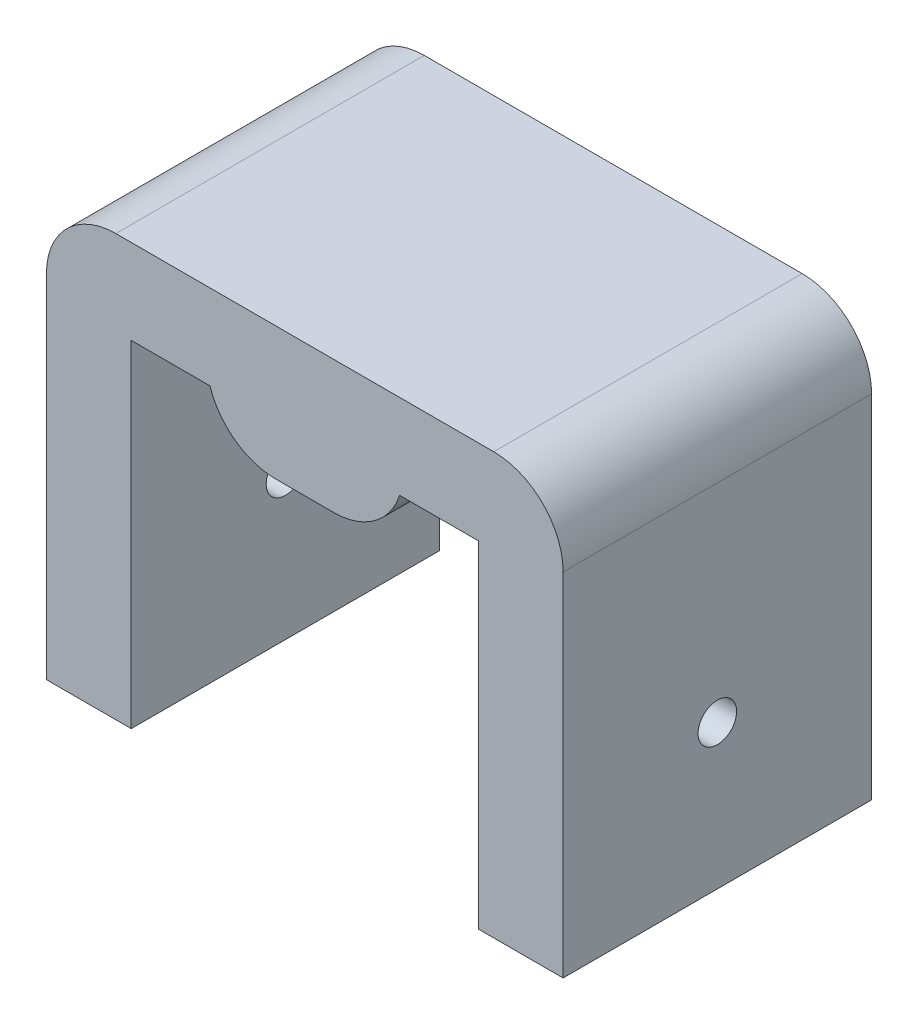
SolidWorks part; units mm, degrees
ref_plane "Front Plane" through (0, 0, 0) normal (0, 0, 1) x (1, 0, 0)
ref_plane "Top Plane" through (0, 0, 0) normal (0, 1, 0) x (1, 0, 0)
ref_plane "Right Plane" through (0, 0, 0) normal (1, 0, 0) x (0, 0, -1)
sketch "Sketch1" plane through (0, 0, 0) normal (0, 0, 1) x (1, 0, 0)
  line L0 (-16.75, 0) -> (-16.75, 27.3)
  line L1 (-16.75, 27.3) -> (16.75, 27.3)
  line L2 (16.75, 27.3) -> (16.75, 0)
  line L3 (16.75, 0) -> (11.25, 0)
  line L4 (11.25, 0) -> (11.25, 21.8)
  line L5 (11.25, 21.8) -> (6.15, 21.8)
  line L6 (6.15, 21.8) -> (6.15, 18.7)
  line L7 (6.15, 18.7) -> (-6.15, 18.7)
  line L8 (-6.15, 18.7) -> (-6.15, 21.8)
  line L9 (-6.15, 21.8) -> (-11.25, 21.8)
  line L10 (-11.25, 21.8) -> (-11.25, 0)
  line L11 (-11.25, 0) -> (-16.75, 0)
  line L12 (0, 27.3) -> (0, 18.7) construction
  point P11 (0, 18.7)
  dimension "D1" = 5.5
  dimension "D2" = 21.8
  dimension "D3" = 12.3
  dimension "D4" = 22.5
  dimension "D5" = 5.5
  dimension "D6" = 3.1
extrude "Boss-Extrude1" add sketch "Sketch1" along normal blind 20 contours L1 L2 L3 L4 L5 L6 L7 L8 L9 L10 L11 L0
fillet "Fillet1" radius 4.5 2 edges at (16.75, 27.3, 10) (-16.75, 27.3, 10)
fillet "Fillet2" radius 4.5 2 edges at (-6.15, 18.7, 10) (6.15, 18.7, 10)
sketch "Sketch2" plane through (16.75, 0, 0) normal (1, 0, 0) x (0, 0, -1)
  line L0 (-20, 0) -> (0, 18.7) construction
  circle A0 centre (-10, 9.35) radius 1.25
  dimension "D1" = 2.5
extrude "Cut-Extrude1" cut sketch "Sketch2" against normal through all
